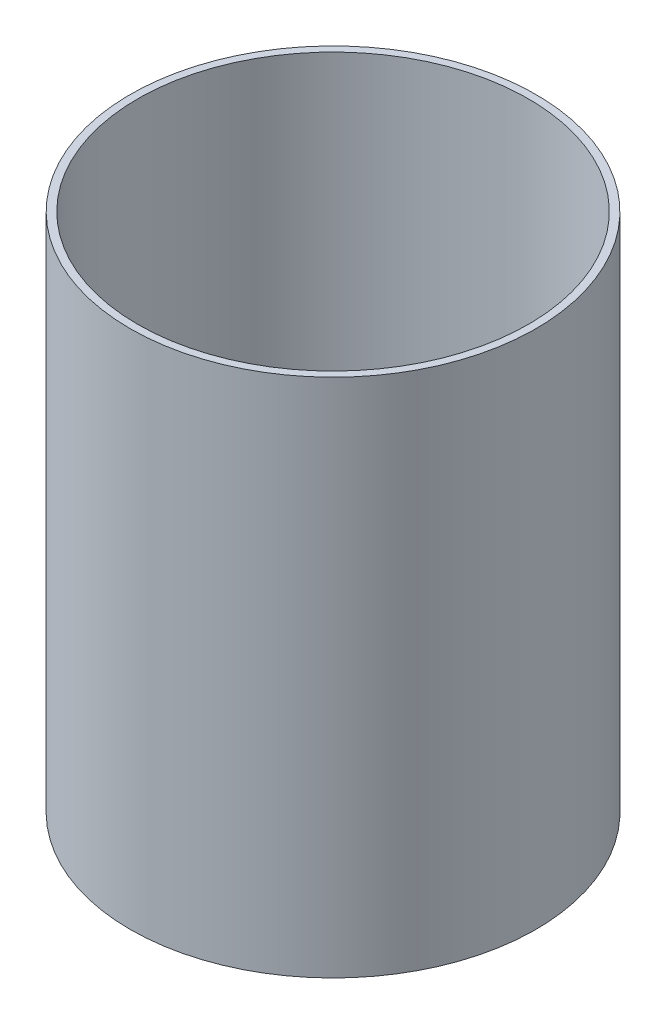
SolidWorks part; units mm, degrees
ref_plane "Front Plane" through (0, 0, 0) normal (0, 0, 1) x (1, 0, 0)
ref_plane "Top Plane" through (0, 0, 0) normal (0, 1, 0) x (1, 0, 0)
ref_plane "Right Plane" through (0, 0, 0) normal (1, 0, 0) x (0, 0, -1)
sketch "Sketch1" plane through (0, 0, 0) normal (0, 1, 0) x (1, 0, 0)
  circle A0 centre (0, 0) radius 49.5173
  circle A1 centre (0, 0) radius 47.6885
  dimension "D1" = 99.0346
  dimension "D2" = 95.377
extrude "Boss-Extrude1" add sketch "Sketch1" along normal blind 127
equation "\"Coupler_OD\"= 3.899in"
equation "\"Coupler_ID\"= 3.755in"
equation "\"Nosecone_Coupler_Length\"= 5in"
equation "\"D1@Sketch1\"=\"Coupler_OD\""
equation "\"D2@Sketch1\"=\"Coupler_ID\""
equation "\"D1@Boss-Extrude1\"=\"Nosecone_Coupler_Length\""
